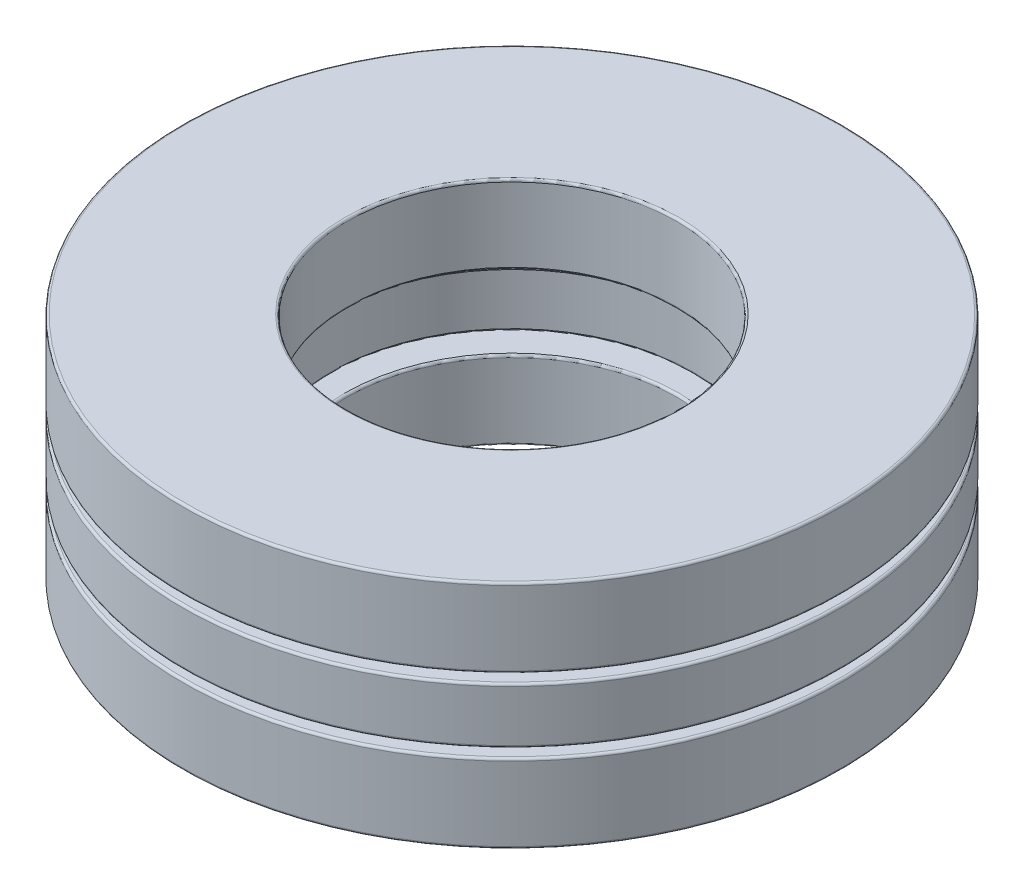
SolidWorks part; units mm, degrees
ref_plane "Front Plane" through (0, 0, 0) normal (0, 0, 1) x (1, 0, 0)
ref_plane "Top Plane" through (0, 0, 0) normal (0, 1, 0) x (1, 0, 0)
ref_plane "Right Plane" through (0, 0, 0) normal (1, 0, 0) x (0, 0, -1)
sketch "Sketch1" plane through (0, 0, 0) normal (0, 0, 1) x (1, 0, 0)
  line L0 (-20, 1.5537) -> (-20, -1.5537)
  line L1 (-19.86, -1.6937) -> (-11.14, -1.6937)
  line L2 (-11, -1.5537) -> (-11, 1.5537)
  line L3 (-11.14, 1.6937) -> (-19.86, 1.6937)
  line L4 (0, -7) -> (0, 7) construction
  line L5 (-20, 6.86) -> (-20, 2.3731)
  line L6 (-19.86, 2.2331) -> (-10.14, 2.2331)
  line L7 (-10, 2.3731) -> (-10, 6.86)
  line L8 (-10.14, 7) -> (-19.86, 7)
  line L9 (-15.5, 2.7725) -> (-15.5, 1.6937) construction
  arc A0 (-20, 1.5537) -> (-19.86, 1.6937) centre (-19.86, 1.5537) cw
  arc A1 (-11.14, 1.6937) -> (-11, 1.5537) centre (-11.14, 1.5537) cw
  arc A2 (-11, -1.5537) -> (-11.14, -1.6937) centre (-11.14, -1.5537) cw
  arc A3 (-19.86, -1.6937) -> (-20, -1.5537) centre (-19.86, -1.5537) cw
  circle A4 centre (-15.5, 0) radius 2.71
  arc A5 (-10.14, 2.2331) -> (-10, 2.3731) centre (-10.14, 2.3731) ccw
  arc A6 (-10, 6.86) -> (-10.14, 7) centre (-10.14, 6.86) ccw
  arc A7 (-19.86, 7) -> (-20, 6.86) centre (-19.86, 6.86) ccw
  arc A8 (-20, 2.3731) -> (-19.86, 2.2331) centre (-19.86, 2.3731) ccw
  circle A9 centre (-15.5, 0) radius 2.7725 construction
  point P15 (-11, 0)
  point P24 (-15.5, 2.2331)
  dimension "D1" = 0.14
  dimension "Thickness" = 14
  dimension "D2" = 3.3875
  dimension "D3" = 0.0625
  dimension "Washer ID" = 20
sketch "Sketch2" plane through (0, 0, 0) normal (0, 0, 1) x (1, 0, 0)
  line L0 (-11, -1.5537) -> (-11, 1.5537) construction
  line L1 (-19.86, -1.6938) -> (-11.14, -1.6937) construction
  line L2 (-20, 1.5537) -> (-20, -1.5537) construction
  line L3 (-11.14, 1.6937) -> (-19.86, 1.6938) construction
  line L4 (-11, -1.5537) -> (-11, 1.5537)
  line L5 (-19.86, -1.6938) -> (-11.14, -1.6937)
  line L6 (-20, 1.5537) -> (-20, -1.5537)
  line L7 (-11.14, 1.6937) -> (-19.86, 1.6938)
  arc A0 (-11, 1.5537) -> (-11.14, 1.6937) centre (-11.14, 1.5537) ccw construction
  arc A1 (-11.14, -1.6937) -> (-11, -1.5537) centre (-11.14, -1.5537) ccw construction
  arc A2 (-20, -1.5537) -> (-19.86, -1.6938) centre (-19.86, -1.5537) ccw construction
  arc A3 (-19.86, 1.6938) -> (-20, 1.5537) centre (-19.86, 1.5537) ccw construction
  arc A4 (-11, 1.5537) -> (-11.14, 1.6937) centre (-11.14, 1.5537) ccw
  arc A5 (-11.14, -1.6937) -> (-11, -1.5537) centre (-11.14, -1.5537) ccw
  arc A6 (-20, -1.5537) -> (-19.86, -1.6938) centre (-19.86, -1.5537) ccw
  arc A7 (-19.86, 1.6938) -> (-20, 1.5537) centre (-19.86, 1.5537) ccw
revolve "Revolve2" add sketch "Sketch2" angle 360 about L4
sketch "Sketch4" plane through (0, 0, 0) normal (0, 0, 1) x (1, 0, 0)
  line L0 (-7, 0) -> (7, 0) construction
  line L1 (0, -7) -> (0, 7) construction
  line L2 (-10, 2.3731) -> (-10, 6.86) construction
  line L3 (-20, 6.86) -> (-20, 2.3731) construction
  line L5 (-19.86, 2.2331) -> (-17.1431, 2.2331)
  line L6 (-20, 6.86) -> (-20, 2.3731)
  line L10 (-17.1431, 2.2331) -> (-13.8569, 2.2331) construction
  line L11 (-15.5, 2.7725) -> (-15.5, 2.2331) construction
  line L12 (-15.5, 2.7725) -> (-15.5, 2.2331) construction
  line L13 (-15.5, 2.7725) -> (-15.5, 1.6937) construction
  line L14 (-10, 2.3731) -> (-10, 6.86)
  line L15 (-10.14, 7) -> (-19.86, 7) construction
  line L16 (-10.14, 7) -> (-19.86, 7)
  line L17 (-13.8569, 2.2331) -> (-10.14, 2.2331)
  arc A0 (-13.8569, 2.2331) -> (-17.1431, 2.2331) centre (-15.5, 0) ccw
  arc A1 (-10.14, 2.2331) -> (-10, 2.3731) centre (-10.14, 2.3731) ccw construction
  circle A2 centre (-15.5, 0) radius 2.7725 construction
  arc A3 (-10.14, 2.2331) -> (-10, 2.3731) centre (-10.14, 2.3731) ccw
  arc A4 (-10, 6.86) -> (-10.14, 7) centre (-10.14, 6.86) ccw construction
  arc A8 (-20, 2.3731) -> (-19.86, 2.2331) centre (-19.86, 2.3731) ccw
  arc A10 (-10, 6.86) -> (-10.14, 7) centre (-10.14, 6.86) ccw
  arc A11 (-19.86, 7) -> (-20, 6.86) centre (-19.86, 6.86) ccw construction
  arc A12 (-19.86, 7) -> (-20, 6.86) centre (-19.86, 6.86) ccw
revolve "Revolve3" add sketch "Sketch4" angle 360 about L4
mirror "Mirror1" about plane through (0, 0, 0) normal (0, 1, 0) of bodies 107
sketch "Sketch3" plane through (0, 0, 0) normal (0, 0, 1) x (1, 0, 0)
  line L0 (-15.5, 2.7725) -> (-15.5, -2.7725)
  arc A0 (-15.5, 2.7725) -> (-15.5, -2.7725) centre (-15.5, 0) ccw
revolve "Cut-Revolve1" cut sketch "Sketch3" angle 360 about L0
sketch "Sketch5" plane through (0, 0, 0) normal (0, 0, 1) x (1, 0, 0)
  line L0 (-15.5, 2.71) -> (-15.5, -2.71)
  arc A0 (-15.5, 2.71) -> (-15.5, -2.71) centre (-15.5, 0) ccw
  circle A1 centre (-15.5, 0) radius 2.71 construction
revolve "Revolve4" add sketch "Sketch5" angle 360 about L0
pattern_circular "CirPattern2" count 16 over 360 about axis through (0, -7, 0) along (0, 1, 0) of "Cut-Revolve1" reverse direction yes
pattern_circular "CirPattern3" count 16 over 360 about axis through (0, -7, 0) along (0, 1, 0) reverse direction yes of bodies 109
sketch "Sketch6" plane through (0, 0, 0) normal (0, 1, 0) x (1, 0, 0)
  circle A0 centre (0, 0) radius 20
  circle A1 centre (0, 0) radius 10
  dimension "Washer ID" = 20
  dimension "OD" = 40
ref_plane "Contact Plane 1" through (0, 7, 0) normal (0, 1, 0) x (1, 0, 0)
ref_plane "Contact Plane 2" through (0, -7, 0) normal (0, -1, 0) x (-1, 0, 0)
ref_axis "Center Axis 1" through (0, 1.5537, 0) along (0, -1, 0)
equation "\"D2@Sketch1\"=\"Ball Diameter@Sketch1\"*.625"
equation "\"D1@Sketch1\"=\"Thickness@Sketch1\"*.01"
equation "\"D1@CirPattern3\" = \"Balls@CirPattern2\""
